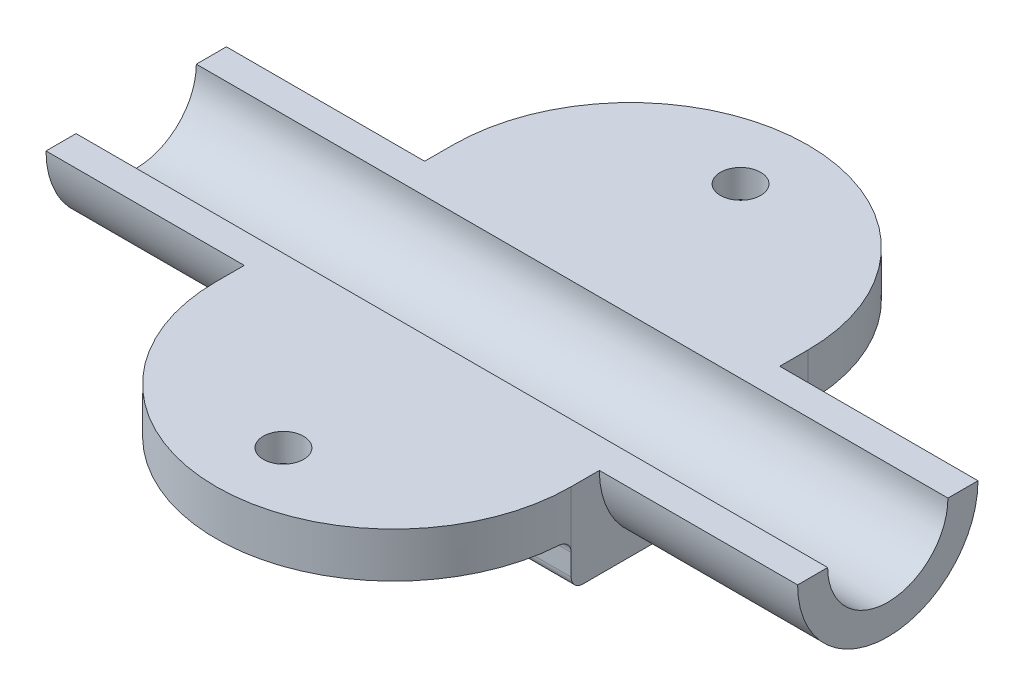
SolidWorks part; units mm, degrees
material "ABS"
ref_plane "Front Plane" through (0, 0, 0) normal (0, 0, 1) x (1, 0, 0)
ref_plane "Top Plane" through (0, 0, 0) normal (0, 1, 0) x (1, 0, 0)
ref_plane "Right Plane" through (0, 0, 0) normal (1, 0, 0) x (0, 0, -1)
sketch "Sketch1" plane through (0, 0, 0) normal (0, 1, 0) x (1, 0, 0)
  line L1 (-15, 15) -> (15, 15)
  line L2 (-15, 15) -> (-15, -15)
  line L3 (-15, -15) -> (15, -15)
  line L4 (15, 15) -> (15, -15)
  line L5 (-15, 15) -> (15, -15) construction
  line L6 (-15, -15) -> (15, 15) construction
  point P0 (0, 0)
  dimension "D1" = 30
  dimension "D2" = 30
extrude "Boss-Extrude1" add sketch "Sketch1" along normal blind 7.62
sketch "Sketch2" plane through (15, 0, 0) normal (1, 0, 0) x (0, 0, -1)
  line L0 (-15, 7.62) -> (15, 7.62) construction
  line L9 (-7.62, 7.62) -> (-5.08, 7.62)
  line L10 (7.62, 7.62) -> (5.08, 7.62)
  arc A0 (-7.62, 7.62) -> (7.62, 7.62) centre (0, 7.62) ccw
  arc A1 (-5.08, 7.62) -> (5.08, 7.62) centre (0, 7.62) ccw
  line M8 (15, 7.62) -> (-15, 7.62)
  dimension "D1" = 15.24
  dimension "D2" = 10.16
extrude "Boss-Extrude2" add sketch "Sketch2" along normal blind 16.75 contours A0 L9 A1 L10
extrude "Cut-Extrude2" cut sketch "Sketch2<4>" against normal through all contours A1 M8 region at (15, 5.464, 0)
sketch "Sketch2<4>" plane through (15, 0, 0) normal (1, 0, 0) x (0, 0, -1) same geometry as "Sketch2"
mirror "Mirror1" about plane through (0, 0, 0) normal (1, 0, 0) of "Boss-Extrude2"
sketch "Sketch3" plane through (0, 0, 15) normal (0, 0, 1) x (1, 0, 0)
  line L0 (15, 7.62) -> (15, 0) construction
  line L1 (-15, 7.62) -> (15, 7.62)
  line L2 (-15, 7.62) -> (-15, 3.81)
  line L3 (-15, 3.81) -> (15, 3.81)
  line L4 (15, 7.62) -> (15, 3.81)
extrude "Boss-Extrude3" add sketch "Sketch3" along normal blind 10
sketch "Sketch5" plane through (0, 7.62, 0) normal (0, 1, 0) x (1, 0, 0)
  line L0 (15, -25) -> (-15, -25) construction
  line L1 (-15, -7.62) -> (-15, -25) construction
  line L2 (-15, -16.31) -> (15, -16.31) construction
  line L3 (15, -25) -> (15, -7.62) construction
  circle A0 centre (0, -19.31) radius 1.25
  point P4 (0, -25)
  dimension "D1" = 2.5
  dimension "D2" = 3
sketch "Sketch8" plane through (0, 3.81, 0) normal (0, -1, 0) x (1, 0, 0)
  point P0 (0, 19.31)
hole_wizard "CSK for M3 Countersunk Flat Head Screw1" positions "3DSketch2" profile "Sketch9" countersink size "M3" standard "ISO" end condition through all
sketch3d "3DSketch2"
  point P0 (0, 3.81, 19.31)
sketch "Sketch9" plane through (0, 3.81, 19.31) normal (1, 0, 0) x (0, 0, -1)
  line L0 (0, 0) -> (0, 3.81)
  line L1 (0, 3.81) -> (1.7, 3.81)
  line L2 (1.7, 3.81) -> (1.7, 1.45)
  line L3 (1.7, 1.45) -> (3.15, 0)
  line L5 (3.15, 0) -> (0, 0)
  line L6 (-1.7, 1.45) -> (-3.15, 0) construction
  line L11 (0, -6.35) -> (0, 107.95) construction
  dimension "Thru Hole Dia." = 3.4
  dimension "Thru Hole Depth" = 3.81
  dimension "Near C'Sink Dia." = 6.3
  dimension "Near C'Sink Angle" = 90
sketch "Sketch4" plane through (0, 7.62, 0) normal (0, 1, 0) x (1, 0, 0)
  line L0 (15, -25) -> (15, -7.62) construction
  line L3 (-15, -7.62) -> (-15, -25) construction
  line L4 (15, -25) -> (-15, -25) construction
  arc A0 (15, -10) -> (-15, -10) centre (0, -10) cw
  line M4 (-15, -7.62) -> (-15, -25)
  line M5 (-15, -25) -> (15, -25)
  line M6 (15, -25) -> (15, -7.62)
extrude "Cut-Extrude3" cut sketch "Sketch4" against normal blind 10 and the other way through all contours A0 M5 M4 | A0 M6 M5 region at (11.6495, 7.62, 21.6495) region at (-11.6495, 7.62, 21.6495)
mirror "Mirror2" about plane through (0, 0, 0) normal (0, 0, 1) of "CSK for M3 Countersunk Flat Head Screw1", "Boss-Extrude3", "Cut-Extrude3"
sketch "Sketch6" plane through (0, 0, 0) normal (0, -1, 0) x (1, 0, 0)
  line L1 (-15, 10) -> (15, 10)
  line L2 (-15, 10) -> (-15, 15)
  line L3 (-15, 15) -> (15, 15)
  line L4 (15, 10) -> (15, 15)
  line L5 (-15, -10) -> (15, -10)
  line L6 (-15, -10) -> (-15, -15)
  line L7 (-15, -15) -> (15, -15)
  line L8 (15, -10) -> (15, -15)
  line L9 (15, 0) -> (15, 7.62) construction
  line L10 (-14.1421, 15) -> (14.1421, 15) construction
  line L11 (14.1421, -15) -> (-14.1421, -15) construction
extrude "Cut-Extrude5" cut sketch "Sketch6" against normal up to surface (3.81 mm away) up to face at (0, 3.81, -22.46)
fillet "Fillet1" radius 1 4 edges at (0, 3.81, 10) (0, 3.81, -10) (0, 0, -10) (0, 0, 10)
